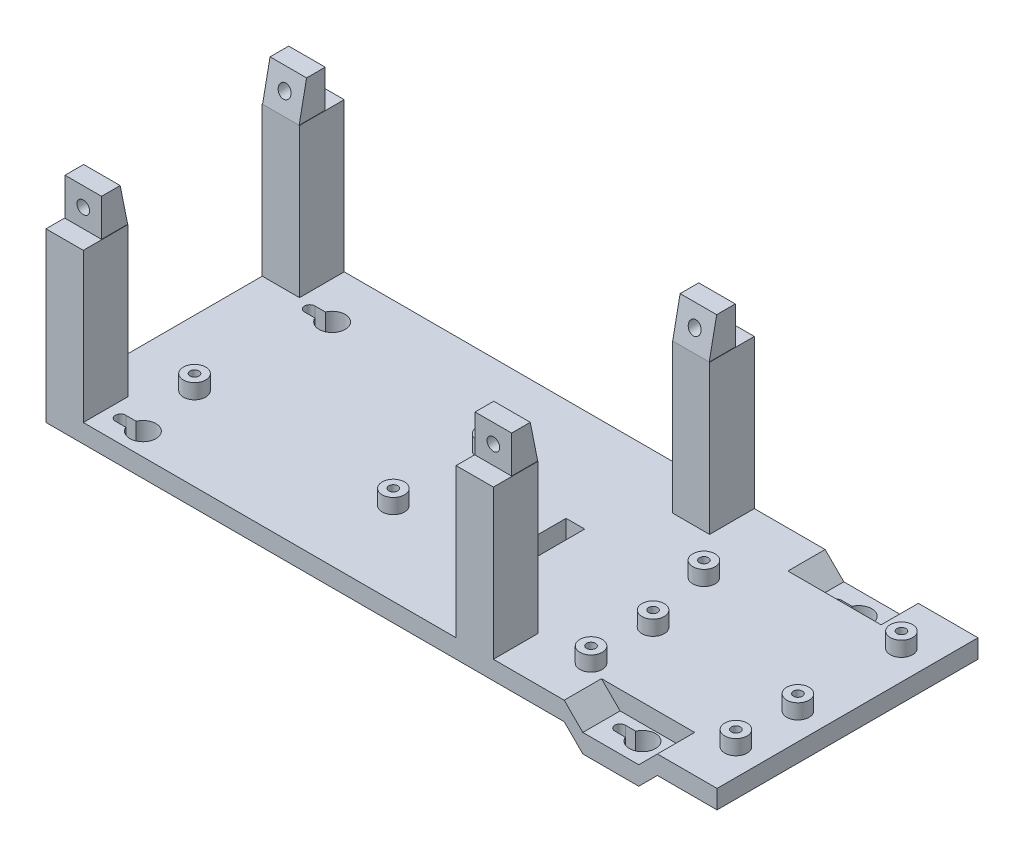
SolidWorks part; units mm, degrees
ref_plane "Front Plane" through (0, 0, 0) normal (0, 0, 1) x (1, 0, 0)
ref_plane "Top Plane" through (0, 0, 0) normal (0, 1, 0) x (1, 0, 0)
ref_plane "Right Plane" through (0, 0, 0) normal (1, 0, 0) x (0, 0, -1)
sketch "Sketch1" plane through (0, 0, 0) normal (0, 1, 0) x (1, 0, 0)
  line L1 (-90, -35) -> (90, -35)
  line L2 (-90, -35) -> (-90, 35)
  line L3 (-90, 35) -> (90, 35)
  line L4 (90, -35) -> (90, 35)
  line L5 (-90, -35) -> (90, 35) construction
  line L6 (-90, 35) -> (90, -35) construction
  point P0 (0, 0)
  dimension "D1" = 180
  dimension "D2" = 70
extrude "Boss-Extrude1" add sketch "Sketch1" along normal blind 5
sketch "Sketch3" plane through (0, 5, 0) normal (0, 1, 0) x (1, 0, 0)
  line L0 (90, 35) -> (-90, 35) construction
  line L1 (69, 35) -> (54, 35)
  line L2 (69, 35) -> (69, 25)
  line L3 (69, 25) -> (54, 25)
  line L4 (54, 35) -> (54, 25)
  line L5 (-90, -35) -> (90, -35) construction
  line L6 (69, -35) -> (54, -35)
  line L7 (69, -35) -> (69, -25)
  line L8 (69, -25) -> (54, -25)
  line L9 (54, -35) -> (54, -25)
  line L10 (90, -35) -> (90, 35) construction
  dimension "D1" = 10
  dimension "D2" = 15
  dimension "D3" = 21
extrude "Cut-Extrude1" cut sketch "Sketch3" against normal blind 6
chamfer "Chamfer2" distance 5 angle 45 4 edges at (54, 5, 30) (69, 5, 30) (69, 5, -30) (54, 5, -30)
sketch "Sketch5" plane through (0, 0, 0) normal (0, -1, 0) x (1, 0, 0)
  line L0 (-90, 35) -> (54, 35) construction
  line L1 (49, 35) -> (74, 35)
  line L2 (49, 35) -> (49, 23)
  line L3 (49, 23) -> (74, 23)
  line L4 (74, 35) -> (74, 23)
  line L5 (54, -35) -> (-90, -35) construction
  line L6 (49, -35) -> (74, -35)
  line L7 (49, -35) -> (49, -23)
  line L8 (49, -23) -> (74, -23)
  line L9 (74, -35) -> (74, -23)
  line L10 (74, 25) -> (74, 35) construction
  line L11 (49, 35) -> (49, 25) construction
  dimension "D1" = 12
extrude "Boss-Extrude7" add sketch "Sketch5" along normal blind 5
chamfer "Chamfer4" distance 5 angle 45 4 edges at (49, -5, 29) (74, -5, 29) (74, -5, -29) (49, -5, -29)
sketch "Sketch6" plane through (0, 0, 0) normal (0, 1, 0) x (1, 0, 0)
  line L0 (58, -29) -> (64, -29) construction
  line L1 (58, -27.6) -> (64, -27.6)
  line L2 (58, -30.4) -> (64, -30.4)
  line L3 (69, -35) -> (54, -35) construction
  line L5 (58, 29) -> (64, 29) construction
  line L6 (58, 30.4) -> (64, 30.4)
  line L7 (58, 27.6) -> (64, 27.6)
  line L8 (54, 35) -> (69, 35) construction
  line L9 (69, -25) -> (69, -35) construction
  circle A0 centre (64, -29) radius 3.5
  arc A1 (58, -27.6) -> (58, -30.4) centre (58, -29) ccw
  arc A2 (64, -30.4) -> (64, -27.6) centre (64, -29) ccw
  circle A3 centre (64, 29) radius 3.5
  arc A4 (58, 30.4) -> (58, 27.6) centre (58, 29) ccw
  arc A5 (64, 27.6) -> (64, 30.4) centre (64, 29) ccw
  point P2 (61, -29)
  point P15 (61, 29)
  dimension "D1" = 7
  dimension "D2" = 2.8
  dimension "D3" = 6
  dimension "D4" = 5
  dimension "D5" = 6
  dimension "D6" = 6
extrude "Cut-Extrude2" cut sketch "Sketch6" against normal through all contours A4 L6 A0 L7 | L6 A4 L7 A0 | L7 A5 L6 A0 | L1 A1 L2 | L2 A2 L1 | A2 L2 A0 L1 region at (58.7359, 0, 29) region at (64.6953, 0, 25.6687) region at (62.8576, 0, 29) region at (58.7359, 0, -29) region at (64.6953, 0, -32.3313) region at (62.8576, 0, -29)
sketch "Sketch7" plane through (0, 5, 0) normal (0, 1, 0) x (1, 0, 0)
  line L0 (-76, -29) -> (-70, -29) construction
  line L1 (-76, -27.6) -> (-70, -27.6)
  line L2 (-76, -30.4) -> (-70, -30.4)
  line L4 (-90, -35) -> (49, -35) construction
  line L5 (-90, 35) -> (-90, -35) construction
  line L6 (-76, 21.75) -> (-70, 21.75) construction
  line L7 (-76, 23.15) -> (-70, 23.15)
  line L8 (-76, 20.35) -> (-70, 20.35)
  circle A0 centre (-70, -29) radius 3.5
  arc A1 (-76, -27.6) -> (-76, -30.4) centre (-76, -29) ccw
  arc A2 (-70, -30.4) -> (-70, -27.6) centre (-70, -29) ccw
  circle A3 centre (-70, 21.75) radius 3.5
  arc A4 (-76, 23.15) -> (-76, 20.35) centre (-76, 21.75) ccw
  arc A5 (-70, 20.35) -> (-70, 23.15) centre (-70, 21.75) ccw
  point P3 (-73, -29)
  point P14 (-73, 21.75)
  dimension "D3" = 7
  dimension "D6" = 50.75
  dimension "D1" = 6
  dimension "D2" = 2.8
  dimension "D4" = 6
  dimension "D5" = 20
extrude "Cut-Extrude3" cut sketch "Sketch7" against normal through all contours A2 L2 A0 L1 | A5 L8 A3 L7 | L1 A2 L2 A1 | L8 A5 L7 A4 region at (-69.3047, 5, 25.6687) region at (-69.3047, 5, -25.0813)
sketch "Sketch8" plane through (0, 5, 0) normal (0, 1, 0) x (1, 0, 0)
  line L0 (-90, -35) -> (49, -35) construction
  line L1 (-90, -35) -> (-80, -35)
  line L2 (-90, -35) -> (-90, -23)
  line L3 (-90, -23) -> (-80, -23)
  line L4 (-80, -35) -> (-80, -23)
  line L5 (-90, 35) -> (-80, 35)
  line L6 (-90, 35) -> (-90, 23)
  line L7 (-90, 23) -> (-80, 23)
  line L8 (-80, 35) -> (-80, 23)
  line L9 (30, -35) -> (20, -35)
  line L10 (30, -35) -> (30, -23)
  line L11 (30, -23) -> (20, -23)
  line L12 (20, -35) -> (20, -23)
  line L13 (30, 35) -> (20, 35)
  line L14 (30, 35) -> (30, 23)
  line L15 (30, 23) -> (20, 23)
  line L16 (20, 35) -> (20, 23)
  line L17 (49, 35) -> (-90, 35) construction
  dimension "D1" = 10
  dimension "D2" = 12
  dimension "D3" = 120
extrude "Boss-Extrude8" add sketch "Sketch8" along normal blind 40
hole_wizard "M2 Clearance Hole1" positions "Sketch15" profile "Sketch14" hole size "M2" standard "ANSI Metric"
sketch "Sketch15" plane through (0, 5, 0) normal (0, 1, 0) x (1, 0, 0)
  circle A0 centre (-11.9765, 2.0955) radius 1.0414 construction
  circle A1 centre (4.5335, -12.5095) radius 1.0414 construction
  circle A2 centre (43.979, -22.7775) radius 1.0922 construction
  circle A3 centre (43.979, -6.1405) radius 1.0922 construction
  circle A4 centre (82.841, -22.7775) radius 1.0922 construction
  circle A5 centre (82.841, -6.1405) radius 1.0922 construction
  circle A7 centre (39.235, 12.25) radius 1.0922 construction
  point P0 (43.979, -22.7775)
  point P2 (43.979, -6.1405)
  point P4 (82.841, -6.1405)
  point P6 (82.841, -22.7775)
  point P8 (82.1869, 22.2793)
  point P10 (39.235, 12.25)
  point P12 (4.5335, -12.5095)
  point P14 (-11.9765, 2.0955)
sketch "Sketch14" plane through (43.979, 5, 22.7775) normal (1, 0, 0) x (0, 0, 1)
  line L0 (0, 0) -> (0, 65.741)
  line L1 (0, 65.741) -> (1.2, 65.02)
  line L2 (1.2, 65.02) -> (1.2, 0)
  line L5 (1.2, 0) -> (0, 0)
  line L10 (0, 65.741) -> (-1.2, 65.02) construction
  line L11 (0, -6.35) -> (0, 107.95) construction
  dimension "Hole Dia." = 2.4
  dimension "Hole Depth" = 65.02
  dimension "Drill Angle" = 118
hole_wizard "M2 Clearance Hole2" positions "Sketch21" profile "Sketch20" hole size "M2" standard "ANSI Metric" end condition through all
sketch "Sketch21" plane through (0, 5, 0) normal (0, 1, 0) x (1, 0, 0)
  circle A0 centre (-19.12, -12.7) radius 1.0922 construction
  circle A1 centre (-19.12, 12.7) radius 1.0922 construction
  circle A2 centre (-72.46, -12.7) radius 1.0922 construction
  point P0 (-19.12, 12.7)
  point P2 (-19.12, -12.7)
  point P4 (-72.46, -12.7)
sketch "Sketch20" plane through (-19.12, 5, -12.7) normal (1, 0, 0) x (0, 0, 1)
  line L0 (0, 0) -> (0, 10)
  line L1 (0, 10) -> (1.2, 10)
  line L2 (1.2, 10) -> (1.2, 0)
  line L5 (1.2, 0) -> (0, 0)
  line L11 (0, -6.35) -> (0, 107.95) construction
  dimension "Thru Hole Dia." = 2.4
  dimension "Thru Hole Depth" = 10
sketch "Sketch17" plane through (0, 5, 0) normal (0, 1, 0) x (1, 0, 0)
  circle A0 centre (-19.12, 12.7) radius 3
  circle A1 centre (82.1869, 22.2793) radius 3
  circle A2 centre (-19.12, -12.7) radius 3
  circle A3 centre (39.235, 12.25) radius 3
  circle A4 centre (-72.46, -12.7) radius 3
  circle A5 centre (43.979, -6.1405) radius 3
  circle A7 centre (43.979, -22.7775) radius 3
  circle A9 centre (82.841, -22.7775) radius 3
  circle A11 centre (82.841, -6.1405) radius 3
  circle A13 centre (4.5335, -12.5095) radius 3
  circle A15 centre (-11.9765, 2.0955) radius 3
  circle M1 centre (43.979, -6.1405) radius 1.2
  circle M2 centre (82.1869, 22.2793) radius 1.2
  circle M3 centre (39.235, 12.25) radius 1.2
  circle M4 centre (4.5335, -12.5095) radius 1.2
  circle M5 centre (-11.9765, 2.0955) radius 1.2
  line M25 (20, -23) -> (30, -23)
  circle M38 centre (82.841, -22.7775) radius 1.2
  circle M39 centre (82.841, -6.1405) radius 1.2
  circle M40 centre (43.979, -22.7775) radius 1.2
  circle M49 centre (-19.12, 12.7) radius 1.2
  circle M50 centre (-72.46, -12.7) radius 1.2
  circle M51 centre (-19.12, -12.7) radius 1.2
  dimension "D1" = 6
extrude "Boss-Extrude9" add sketch "Sketch17" along normal blind 4 contours A1 M2 | A11 M39 | A9 M38 | A7 M40 | A5 M1 | A3 M3 | A13 M25 M4 | A15 M5 | A0 M49 | A2 M51 | A4 M50 region at (-22.0351, 5, -12.7) region at (79.2717, 5, -22.2793) region at (-22.0351, 5, 12.7) region at (36.3199, 5, -12.25) region at (-75.3751, 5, 12.7) region at (41.0639, 5, 6.1405) region at (41.0639, 5, 22.7775) region at (79.9259, 5, 22.7775) region at (79.9259, 5, 6.1405) region at (1.6184, 5, 12.5095) region at (-14.8916, 5, -2.0955)
sketch "Sketch22" plane through (0, 5, 0) normal (0, 1, 0) x (1, 0, 0)
  line L0 (12.01, 7.5) -> (7.01, 7.5)
  line L1 (12.01, 7.5) -> (12.01, -7.5)
  line L2 (7.01, 7.5) -> (7.01, -7.5)
  line L3 (12.01, -7.5) -> (7.01, -7.5)
  line L4 (12.01, 7.5) -> (7.01, -7.5) construction
  line L5 (7.01, 7.5) -> (12.01, -7.5) construction
  line L6 (7.01, -15.24) -> (7.01, 15.24) construction
  line L7 (90, 0) -> (-90, 0) construction
  line L8 (90, -35) -> (90, 35) construction
  line L9 (-90, 23) -> (-90, -23) construction
  point P1 (9.51, 0)
  dimension "D1" = 5
  dimension "D2" = 15
extrude "Cut-Extrude6" cut sketch "Sketch22" against normal through all
sketch "Sketch24" plane through (30, 0, 0) normal (1, 0, 0) x (0, 0, -1)
  line L0 (-30, 45) -> (-30, 55)
  line L1 (-35, 45) -> (-23, 45) construction
  line L2 (-30, 55) -> (-25, 55)
  line L4 (-25, 55) -> (-23, 45)
  line L5 (30, 45) -> (30, 55)
  line L6 (23, 45) -> (35, 45) construction
  line L7 (30, 55) -> (25, 55)
  line L8 (25, 55) -> (23, 45)
  line L9 (-23, 45) -> (-23, 5) construction
  line L10 (-30, 45) -> (-23, 45)
  line L11 (23, 45) -> (30, 45)
  dimension "D1" = 10
  dimension "D2" = 2
  dimension "D3" = 2
  dimension "D4" = 7
extrude "Boss-Extrude10" add sketch "Sketch24" against normal blind 9.8 from offset 0.1 offset against normal yes
pattern_linear "LPattern1" count 2 spacing 110 along (-1, 0, 0) of "Boss-Extrude10"
sketch "Sketch25" plane through (0, 0, -35) normal (0, 0, -1) x (-1, 0, 0)
  line L0 (-30, 45) -> (-30, 5) construction
  line L1 (80, 45) -> (80, 5) construction
  line L2 (80, 45) -> (90, 45) construction
  circle A0 centre (-25, 50) radius 1.7
  circle A1 centre (85, 50) radius 1.7
  dimension "D4" = 3.4
  dimension "D1" = 5
  dimension "D2" = 5
  dimension "D3" = 5
extrude "Cut-Extrude7" cut sketch "Sketch25" against normal through all
equation "\"D6@Sketch6\"=\"D3@Sketch6\""
equation "\"D3@Sketch24\"=\"D2@Sketch24\""
equation "\"D2@Sketch25\"=\"D1@Sketch25\""
